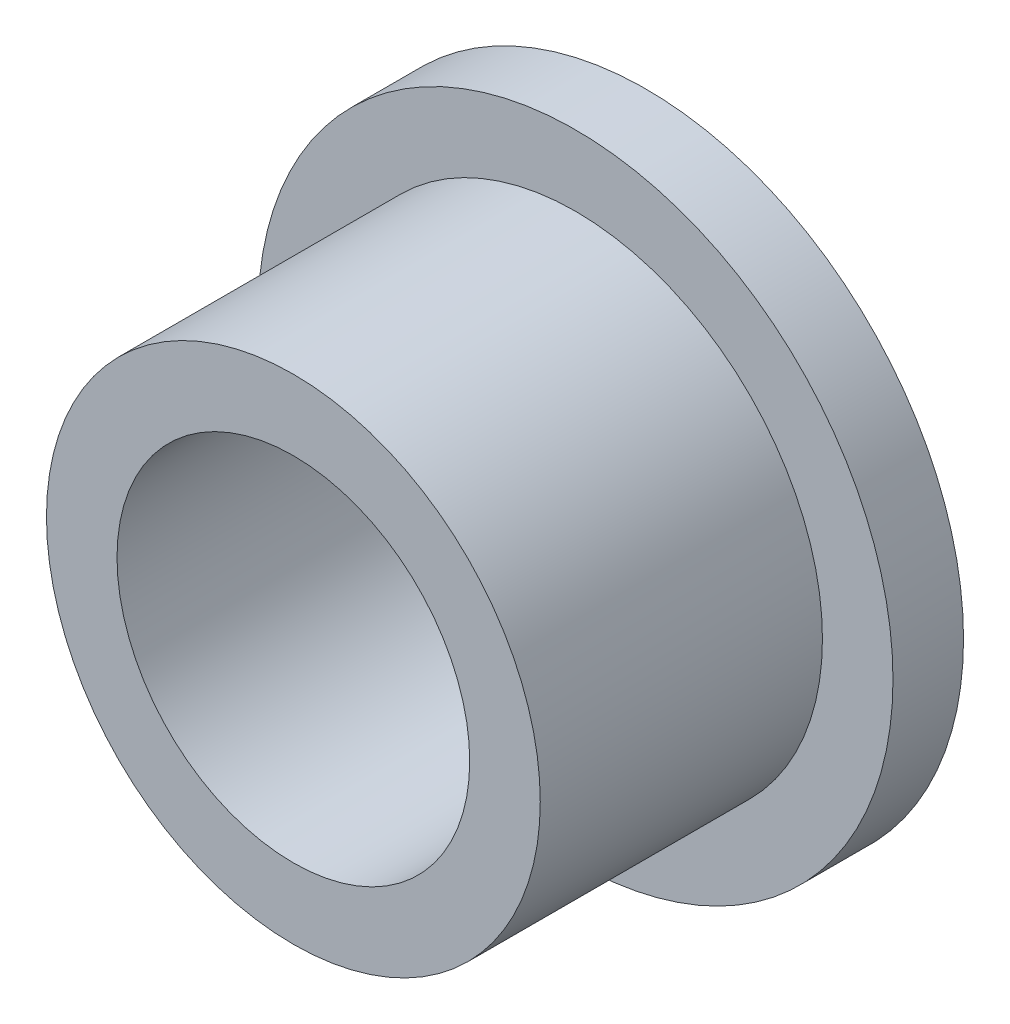
SolidWorks part; units mm, degrees
material "锡轴承青铜"
ref_plane "前视基准面" through (0, 0, 0) normal (0, 0, 1) x (1, 0, 0)
ref_plane "上视基准面" through (0, 0, 0) normal (0, 1, 0) x (1, 0, 0)
ref_plane "右视基准面" through (0, 0, 0) normal (1, 0, 0) x (0, 0, -1)
sketch "草图1" plane through (0, 0, 0) normal (0, 0, 1) x (1, 0, 0)
  circle A0 centre (0, 0) radius 12.5
  circle A1 centre (0, 0) radius 17.5
  circle A2 centre (0, 0) radius 22.5
  dimension "D1" = 25
  dimension "D2" = 35
  dimension "D3" = 45
extrude "凸台-拉伸1" add sketch "草图1" along normal blind 20 contours A1 A0 region at (-17.005, 0, 0)
extrude "凸台-拉伸2" add sketch "草图1<3>" against normal blind 5 contours A2 A1 | A1 A0 region at (-17.005, 0, 0) region at (-21.8636, 0, 0)
sketch "草图1<3>" plane through (0, 0, 0) normal (0, 0, 1) x (1, 0, 0) same geometry as "草图1"
